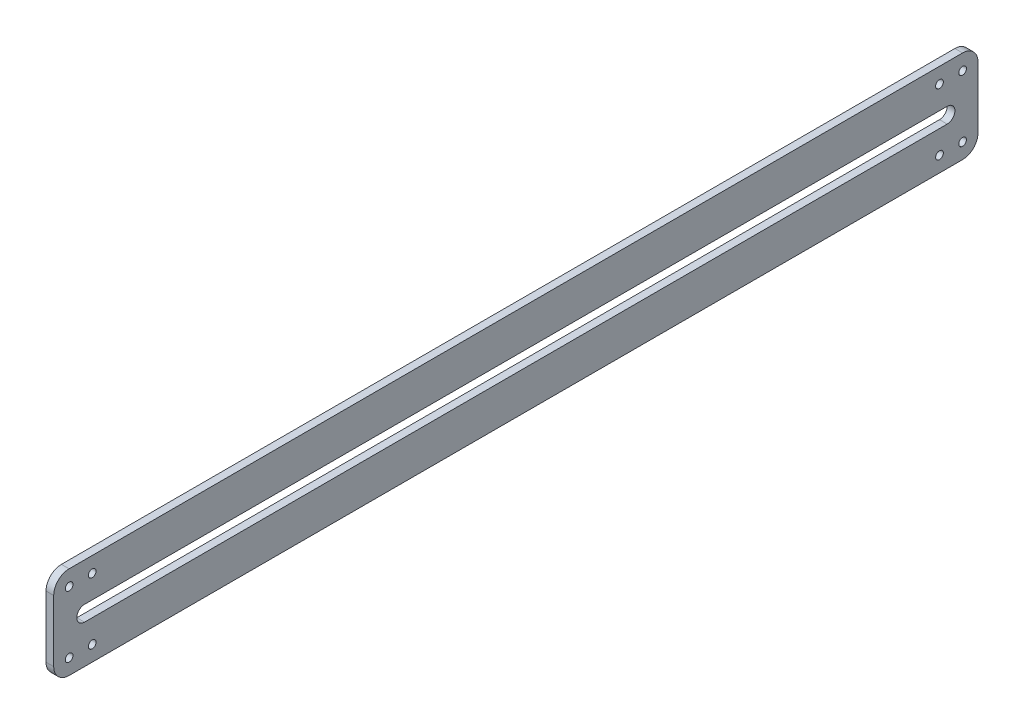
SolidWorks part; units mm, degrees
ref_plane "Front Plane" through (0, 0, 0) normal (0, 0, 1) x (1, 0, 0)
ref_plane "Top Plane" through (0, 0, 0) normal (0, 1, 0) x (1, 0, 0)
ref_plane "Right Plane" through (0, 0, 0) normal (1, 0, 0) x (0, 0, -1)
sketch "Sketch1" plane through (0, 0, 0) normal (1, 0, 0) x (0, 0, -1)
  line L1 (-184.15, -19.05) -> (184.15, -19.05)
  line L2 (-190.5, -12.7) -> (-190.5, 12.7)
  line L3 (-184.15, 19.05) -> (184.15, 19.05)
  line L4 (190.5, -12.7) -> (190.5, 12.7)
  line L5 (-190.5, -19.05) -> (190.5, 19.05) construction
  line L6 (-190.5, 19.05) -> (190.5, -19.05) construction
  arc A0 (184.15, 19.05) -> (190.5, 12.7) centre (184.15, 12.7) cw
  arc A1 (190.5, -12.7) -> (184.15, -19.05) centre (184.15, -12.7) cw
  arc A2 (-184.15, -19.05) -> (-190.5, -12.7) centre (-184.15, -12.7) cw
  arc A3 (-190.5, 12.7) -> (-184.15, 19.05) centre (-184.15, 12.7) cw
  point P0 (0, 0)
  dimension "D3" = 6.35
  dimension "D1" = 381
  dimension "D2" = 38.1
extrude "Outer Cut" add sketch "Sketch1" along normal mid plane 3.175
sketch "Sketch2" plane through (1.5875, 0, 0) normal (1, 0, 0) x (0, 0, -1)
  line L0 (-190.5, 0) -> (190.5, 0) construction
  line L1 (-190.5, 12.7) -> (-190.5, -12.7) construction
  line L2 (190.5, -12.7) -> (190.5, 12.7) construction
  line L3 (-177.8, 0) -> (177.8, 0) construction
  line L4 (-177.8, 3.175) -> (177.8, 3.175)
  line L5 (-177.8, -3.175) -> (177.8, -3.175)
  arc A0 (-177.8, 3.175) -> (-177.8, -3.175) centre (-177.8, 0) ccw
  arc A1 (177.8, -3.175) -> (177.8, 3.175) centre (177.8, 0) ccw
  point P2 (0, 0)
  point P14 (0, 0)
  dimension "D1" = 6.35
  dimension "D3" = 12.7
  dimension "D4" = 12.7
extrude "Slots" cut sketch "Sketch2" against normal through all
sketch "Sketch3" plane through (1.5875, 0, 0) normal (1, 0, 0) x (0, 0, -1)
  line L0 (-190.5, 12.7) -> (-190.5, -12.7) construction
  line L1 (184.15, 19.05) -> (-184.15, 19.05) construction
  line L2 (0, 0) -> (0, 19.05) construction
  line L3 (0, 0) -> (-190.5, 0) construction
  circle A0 centre (-184.15, 12.7) radius 1.5875
  circle A1 centre (-174.625, 12.7) radius 1.5875
  circle A2 centre (-174.625, -12.7) radius 1.5875
  circle A3 centre (-184.15, -12.7) radius 1.5875
  circle A4 centre (174.625, 12.7) radius 1.5875
  circle A5 centre (184.15, 12.7) radius 1.5875
  circle A6 centre (184.15, -12.7) radius 1.5875
  circle A7 centre (174.625, -12.7) radius 1.5875
  dimension "D1" = 3.175
  dimension "D2" = 6.35
  dimension "D3" = 6.35
  dimension "D5" = 9.525
  dimension "D4" = 2
extrude "Mount Holes" cut sketch "Sketch3" against normal through all
